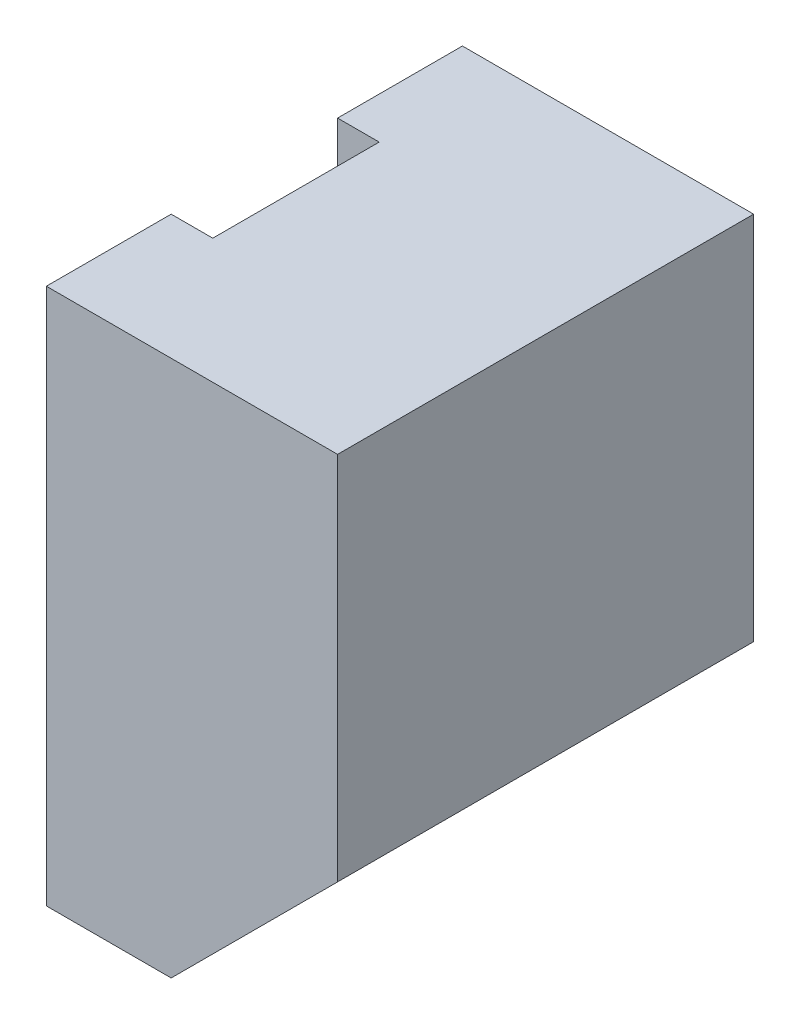
SolidWorks part; units mm, degrees
material "K110"
ref_plane "Front Plane" through (0, 0, 0) normal (0, 0, 1) x (1, 0, 0)
ref_plane "Top Plane" through (0, 0, 0) normal (0, 1, 0) x (1, 0, 0)
ref_plane "Right Plane" through (0, 0, 0) normal (1, 0, 0) x (0, 0, -1)
sketch "Sketch1" plane through (0, 0, 0) normal (0, 1, 0) x (1, 0, 0)
  line L1 (-17.5, -25) -> (17.5, -25)
  line L2 (-17.5, -25) -> (-17.5, 25)
  line L3 (-17.5, 25) -> (17.5, 25)
  line L4 (17.5, -25) -> (17.5, 25)
  line L5 (-17.5, -25) -> (17.5, 25) construction
  line L6 (-17.5, 25) -> (17.5, -25) construction
  point P0 (0, 0)
  dimension "D1" = 50
  dimension "D2" = 35
extrude "Boss-Extrude1" add sketch "Sketch1" against normal blind 64.5
sketch "Sketch2" plane through (0, 0, 25) normal (0, 0, 1) x (1, 0, 0)
  line L0 (-2.5, -64.5) -> (17.5, -44.5)
  line L1 (-17.5, -64.5) -> (17.5, -64.5) construction
  line L2 (17.5, -64.5) -> (17.5, 0) construction
  line L3 (17.5, -44.5) -> (17.5, -64.5)
  line L4 (17.5, -64.5) -> (-2.5, -64.5)
  dimension "D1" = 20
  dimension "D2" = 45
extrude "Cut-Extrude1" cut sketch "Sketch2" against normal up to next
sketch "Sketch3" plane through (-17.5, 0, 0) normal (-1, 0, 0) x (0, 0, 1)
  line L0 (-25, -64.5) -> (25, -64.5) construction
  line L1 (-7, -64.5) -> (7, -64.5)
  line L2 (-7, -64.5) -> (-7, -44.5)
  line L3 (-7, -44.5) -> (7, -44.5)
  line L4 (7, -64.5) -> (7, -44.5)
  line L5 (-25, -44.5) -> (25, -44.5) construction
  point P8 (0, -44.5)
  dimension "D1" = 14
  dimension "D2" = 20
extrude "Cut-Extrude2" cut sketch "Sketch3" against normal up to next
fillet "Fillet1" 2 edges at (0, -44.5, -7) (0, -44.5, 7) type full round first side face at (-5, -54.5, -7) second side face at (-5, -54.5, 7) middle face at (0, -44.5, 0)
sketch "Sketch4" plane through (0, 0, 0) normal (0, 1, 0) x (1, 0, 0)
  line L0 (-17.5, 0) -> (17.5, 0) construction
  line L1 (-17.5, 25) -> (-17.5, -25) construction
  line L2 (17.5, -25) -> (17.5, 25) construction
  line L4 (-17.5, -10) -> (-12.5, -10)
  line L5 (-17.5, -10) -> (-17.5, 10)
  line L6 (-17.5, 10) -> (-12.5, 10)
  line L7 (-12.5, -10) -> (-12.5, 10)
  dimension "D1" = 5
  dimension "D2" = 20
extrude "Cut-Extrude3" cut sketch "Sketch4" against normal blind 43
sketch "Sketch5" plane through (-17.5, 0, 0) normal (-1, 0, 0) x (0, 0, 1)
  line L0 (-10, -43) -> (-10, 0) construction
  line L1 (-15, -43) -> (15, -43)
  line L2 (-15, -43) -> (-15, -38)
  line L3 (-15, -38) -> (15, -38)
  line L4 (15, -43) -> (15, -38)
  line L5 (-10, -43) -> (10, -43) construction
  line L6 (10, -43) -> (10, 0) construction
  dimension "D1" = 5
  dimension "D2" = 5
  dimension "D3" = 5
extrude "Cut-Extrude4" cut sketch "Sketch5" against normal up to surface (5 mm away) up to face at (-12.5, -21.5, 0)
fillet "Fillet5" 2 edges at (-15, -43, -15) (-15, -38, -15) type full round first side face at (-15, -43, 0) second side face at (-15, -38, -12.5) middle face at (-15, -40.5, -15)
fillet "Fillet6" 2 edges at (-15, -43, 15) (-15, -38, 15) type full round first side face at (-15, -43, 1.25) second side face at (-15, -38, 12.5) middle face at (-15, -40.5, 15)
